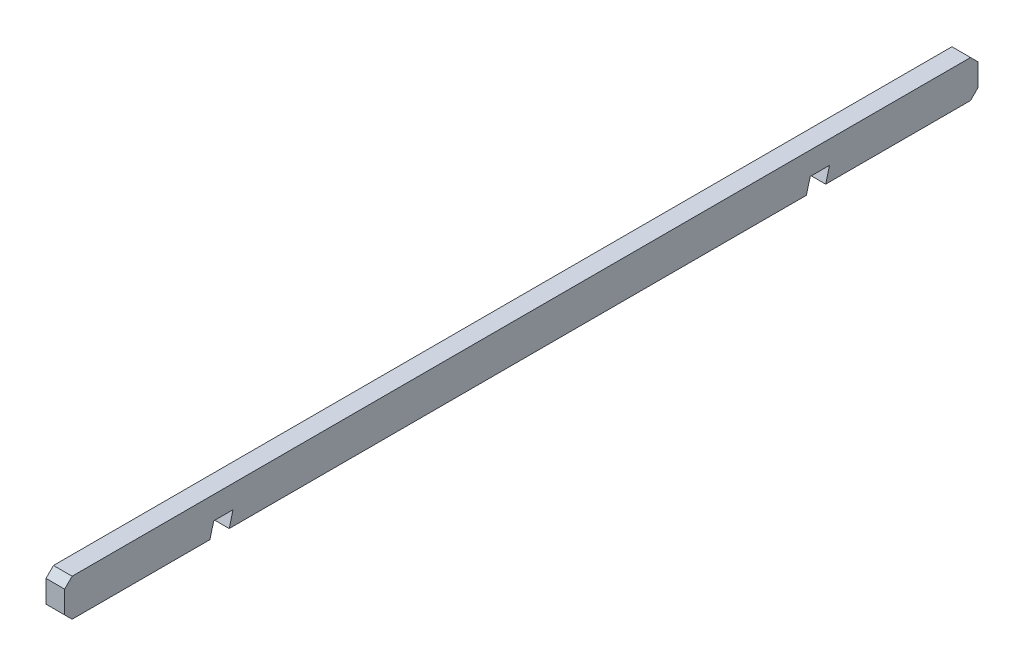
SolidWorks part; units mm, degrees
ref_plane "Front" through (0, 0, 0) normal (0, 0, 1) x (1, 0, 0)
ref_plane "Top" through (0, 0, 0) normal (0, 1, 0) x (1, 0, 0)
ref_plane "Right" through (0, 0, 0) normal (1, 0, 0) x (0, 0, -1)
sketch "Esquisse1" plane through (0, 0, 0) normal (0, 0, 1) x (1, 0, 0)
  line L1 (0, 0) -> (50, 0)
  line L2 (0, 0) -> (0, 100)
  line L3 (0, 100) -> (50, 100)
  line L4 (50, 0) -> (50, 100)
  dimension "D1" = 50
  dimension "D2" = 100
extrude "Boss.-Extru.1" add sketch "Esquisse1" along normal blind 2450
sketch "Esquisse2" plane through (0, 0, 0) normal (-1, 0, 0) x (0, 0, 1)
  line L0 (2060.3528, 0) -> (2050, 38.637)
  line L1 (2450, 0) -> (0, 0) construction
  line L2 (2050, 38.637) -> (1998.2362, 38.637)
  line L3 (1998.2362, 38.637) -> (2008.589, 0)
  line L4 (2008.589, 0) -> (2060.3528, 0)
  line L6 (2450, 100) -> (2450, 0) construction
  line L7 (460.3528, 0) -> (450, 38.637)
  line L8 (450, 38.637) -> (398.2362, 38.637)
  line L9 (398.2362, 38.637) -> (408.589, 0)
  line L10 (408.589, 0) -> (460.3528, 0)
  dimension "D1" = 75
  dimension "D2" = 40
  dimension "D3" = 50
  dimension "D4" = 400
  dimension "D6" = 1600
  dimension "D5" = 2
extrude "Enlèv. mat.-Extru.1" cut sketch "Esquisse2" against normal up to vertex (50 mm away) up to point (50, 0, 2450)
sketch "Esquisse3" plane through (0, 0, 0) normal (-1, 0, 0) x (0, 0, 1)
  line L0 (2450, 100) -> (3328.8675, -1422.2432)
  line L1 (3328.8675, -1422.2432) -> (3242.265, -1472.2432)
  line L2 (3242.265, -1472.2432) -> (2392.265, 0)
  line L3 (2450, 0) -> (2060.3528, 0) construction
  line L6 (2392.265, 0) -> (2450, 0)
  line L7 (2450, 100) -> (2450, 0) construction
  line L8 (2450, 0) -> (2450, 100)
  line L9 (2450, 100) -> (0, 100) construction
  dimension "D1" = 120
  dimension "D2" = 100
  dimension "D3" = 1700
chamfer "Chanfrein1" distance 20 angle 45 4 edges at (25, 100, 2450) (25, 0, 2450) (25, 0, 0) (25, 100, 0)
